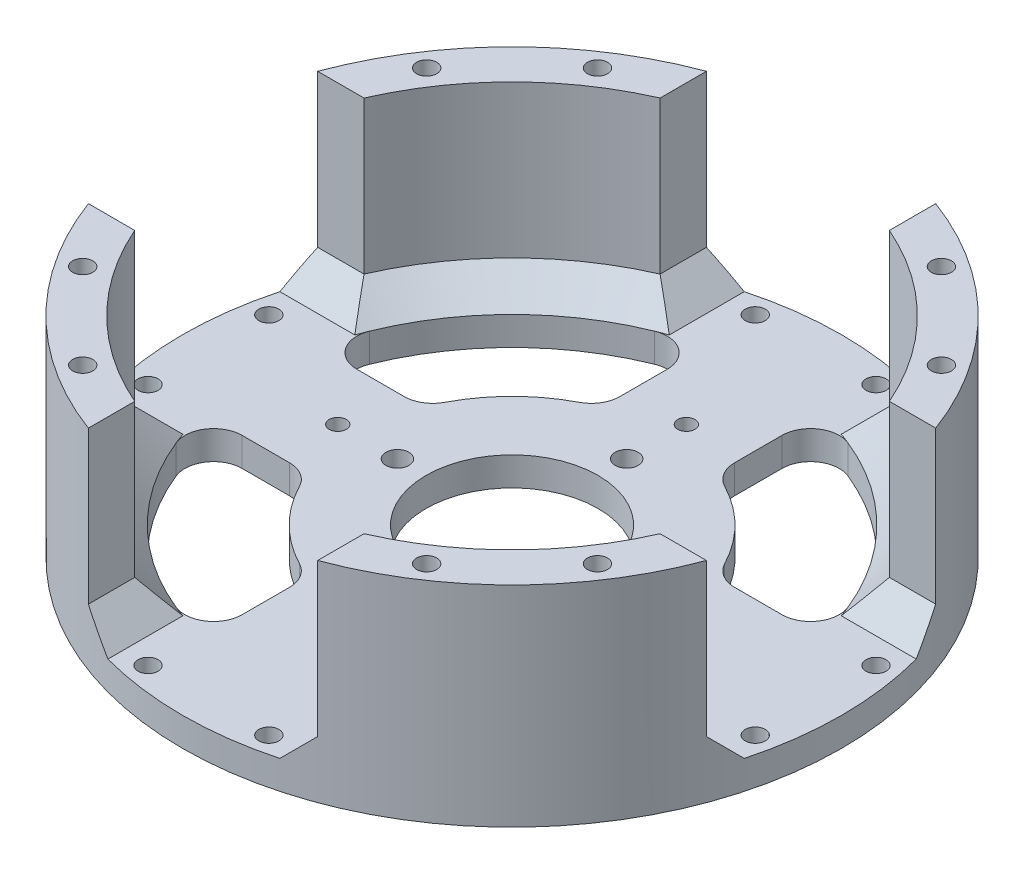
SolidWorks part; units mm, degrees
ref_plane "Front Plane" through (0, 0, 0) normal (0, 0, 1) x (1, 0, 0)
ref_plane "Top Plane" through (0, 0, 0) normal (0, 1, 0) x (1, 0, 0)
ref_plane "Right Plane" through (0, 0, 0) normal (1, 0, 0) x (0, 0, -1)
sketch "Sketch1" plane through (0, 0, 0) normal (0, 1, 0) x (1, 0, 0)
  circle A0 centre (0, 0) radius 57.5
  dimension "D1" = 115
extrude "Boss-Extrude1" add sketch "Sketch1" along normal blind 36.6
sketch "Sketch2" plane through (0, 36.6, 0) normal (0, 1, 0) x (1, 0, 0)
  circle A0 centre (0, 0) radius 50
  dimension "D1" = 100
extrude "Cut-Extrude1" cut sketch "Sketch2" against normal blind 31.6
sketch "Sketch3" plane through (0, 0, 0) normal (0, -1, 0) x (1, 0, 0)
  line L0 (0, 62.4892) -> (0, -59.6631) construction
  line L1 (-72.2237, 0) -> (67.9845, 0) construction
  line L6 (43.8748, 10) -> (43.8748, -10)
  line L7 (43.8748, 10) -> (25.6174, 10)
  line L8 (43.8748, -10) -> (25.6174, -10)
  line L9 (25.6174, 10) -> (25.6174, -10)
  line L10 (-10, -43.8748) -> (10, -43.8748)
  line L11 (-10, -43.8748) -> (-10, -25.6174)
  line L12 (10, -43.8748) -> (10, -25.6174)
  line L13 (-10, -25.6174) -> (10, -25.6174)
  line L14 (-43.8748, 10) -> (-43.8748, -10)
  line L15 (-43.8748, 10) -> (-25.6174, 10)
  line L16 (-43.8748, -10) -> (-25.6174, -10)
  line L17 (-25.6174, 10) -> (-25.6174, -10)
  line L18 (-10, 43.8748) -> (10, 43.8748)
  line L19 (-10, 43.8748) -> (-10, 25.6174)
  line L20 (10, 43.8748) -> (10, 25.6174)
  line L21 (-10, 25.6174) -> (10, 25.6174)
  circle A0 centre (0, 0) radius 20 construction
  circle A1 centre (0, 0) radius 15
  circle A2 centre (0, 20) radius 2
  circle A3 centre (20, 0) radius 2
  circle A4 centre (0, -20) radius 2
  circle A5 centre (-20, 0) radius 2
  circle A6 centre (0, 0) radius 27.5
  circle A7 centre (0, 0) radius 45
  point P15 (0, 0)
  dimension "D1" = 40
  dimension "D2" = 30
  dimension "D3" = 4
  dimension "D5" = 55
  dimension "D6" = 90
  dimension "D7" = 20
  dimension "D4" = 4
extrude "Cut-Extrude2" cut sketch "Sketch3" against normal blind 31.8 contours L19 A7 L15 A6 | L7 A7 L20 A6 | L12 A7 L8 A6 | L16 A7 L11 A6 | A5 | A1 | A2 | A3 | A4
sketch "Sketch4" plane through (0, 0, 0) normal (0, -1, 0) x (1, 0, 0)
  line L0 (0, 0) -> (-10.5349, 52.9624) construction
  line L1 (30.4056, 0) -> (0, 30.4056) construction
  line L2 (0, 30.4056) -> (-30.4056, 0) construction
  line L3 (-30.4056, 0) -> (0, -30.4056) construction
  line L4 (0, -30.4056) -> (30.4056, 0) construction
  line L5 (0, 0) -> (69.7116, 0) construction
  line L6 (0, 0) -> (0, 54) construction
  circle A0 centre (0, 0) radius 54 construction
  circle A13 centre (0, 0) radius 21.5 construction
  circle A14 centre (0, 30.4056) radius 1.5
  circle A15 centre (30.4056, 0) radius 1.5
  circle A16 centre (0, -30.4056) radius 1.5
  circle A17 centre (-30.4056, 0) radius 1.5
  circle A22 centre (-10.5349, 52.9624) radius 1.75
  circle A23 centre (10.5349, 52.9624) radius 1.75
  circle A24 centre (30.0008, 44.8994) radius 1.75
  circle A25 centre (44.8994, 30.0008) radius 1.75
  circle A26 centre (52.9624, 10.5349) radius 1.75
  circle A27 centre (52.9624, -10.5349) radius 1.75
  circle A28 centre (44.8994, -30.0008) radius 1.75
  circle A29 centre (30.0008, -44.8994) radius 1.75
  circle A30 centre (10.5349, -52.9624) radius 1.75
  circle A31 centre (-10.5349, -52.9624) radius 1.75
  circle A32 centre (-30.0008, -44.8994) radius 1.75
  circle A33 centre (-44.8994, -30.0008) radius 1.75
  circle A34 centre (-52.9624, -10.5349) radius 1.75
  circle A35 centre (-52.9624, 10.5349) radius 1.75
  circle A36 centre (-44.8994, 30.0008) radius 1.75
  circle A37 centre (-30.0008, 44.8994) radius 1.75
  point P29 (0, 0)
  point P43 (0, 0)
  point P54 (0, 0)
  dimension "D1" = 108
  dimension "D2" = 11.25
  dimension "D5" = 3
  dimension "D3" = 3.5
  dimension "D4" = 43
  dimension "D7" = 16
  dimension "D6" = 4
extrude "Cut-Extrude3" cut sketch "Sketch4" against normal blind 50
sketch "Sketch6" plane through (0, 0, 0) normal (0, 0, 1) x (1, 0, 0)
  line L0 (0, -2.1266) -> (0, 59.0209)
sketch "Sketch9" plane through (0, 0, 0) normal (0, 0, 1) x (1, 0, 0)
  line L0 (0, -2.1266) -> (0, 59.0209) construction
  line L1 (-20, 36.6) -> (20, 36.6)
  line L2 (-20, 36.6) -> (-20, 5)
  line L3 (-20, 5) -> (20, 5)
  line L4 (20, 36.6) -> (20, 5)
  line L5 (-20, 36.6) -> (20, 5) construction
  line L6 (-20, 5) -> (20, 36.6) construction
  line L7 (50, 36.6) -> (-50, 36.6) construction
  line L8 (-57.5, 0) -> (57.5, 0) construction
  point P0 (0, 20.8)
  dimension "D1" = 5
  dimension "D2" = 40
extrude "Cut-Extrude4" cut sketch "Sketch9" against normal blind 72
pattern_circular "CirPattern1" count 4 over 360 about axis through (0, 0, 0) along (0, 1, 0) of "Cut-Extrude4"
fillet "Fillet2" radius 5 16 edges at (-25.6174, 2.5, 10) (-10, 2.5, 25.6174) (-10, 2.5, 43.8748) (-43.8748, 2.5, 10) (43.8748, 2.5, 10) (25.6174, 2.5, 10) (10, 2.5, 25.6174) (10, 2.5, 43.8748) (10, 2.5, -25.6174) (25.6174, 2.5, -10) (43.8748, 2.5, -10) (10, 2.5, -43.8748) (-25.6174, 2.5, -10) (-10, 2.5, -25.6174) (-10, 2.5, -43.8748) (-43.8748, 2.5, -10)
chamfer "Chamfer1" distance 5 angle 45 12 edges at (-35.3553, 5, -35.3553) (-20, 5, -49.8677) (20, 5, -49.8677) (-35.3553, 5, 35.3553) (35.3553, 5, 35.3553) (35.3553, 5, -35.3553) (-49.8677, 5, 20) (20, 5, 49.8677) (49.8677, 5, -20) (49.8677, 5, 20) (-20, 5, 49.8677) (-49.8677, 5, -20)
